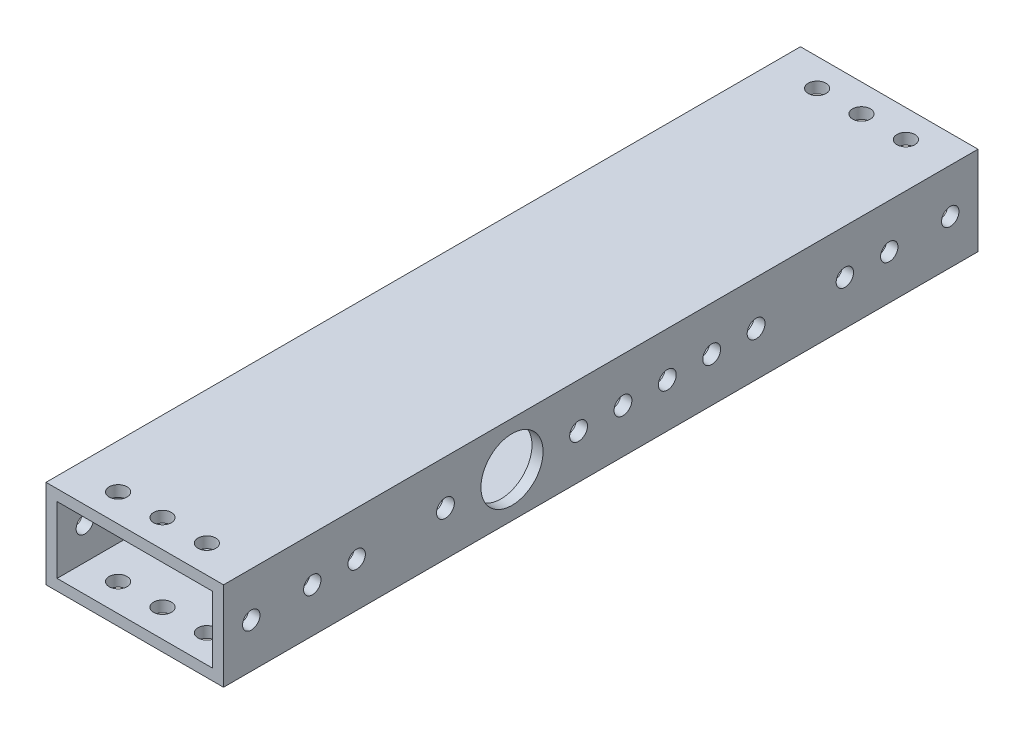
SolidWorks part; units mm, degrees
material "6061-T6 (SS)"
ref_plane "Front Plane" through (0, 0, 0) normal (0, 0, 1) x (1, 0, 0)
ref_plane "Top Plane" through (0, 0, 0) normal (0, 1, 0) x (1, 0, 0)
ref_plane "Right Plane" through (0, 0, 0) normal (1, 0, 0) x (0, 0, -1)
sketch "Sketch1" plane through (0, 0, 0) normal (0, 0, 1) x (1, 0, 0)
  line L0 (-22.225, 9.525) -> (22.225, 9.525)
  line L1 (-25.4, -12.7) -> (25.4, -12.7)
  line L2 (-25.4, -12.7) -> (-25.4, 12.7)
  line L3 (-25.4, 12.7) -> (25.4, 12.7)
  line L4 (25.4, -12.7) -> (25.4, 12.7)
  line L5 (-25.4, -12.7) -> (25.4, 12.7) construction
  line L6 (-25.4, 12.7) -> (25.4, -12.7) construction
  line L7 (22.225, -9.525) -> (22.225, 9.525)
  line L8 (-22.225, -9.525) -> (22.225, -9.525)
  line L9 (-22.225, -9.525) -> (-22.225, 9.525)
  point P0 (0, 0)
  dimension "D1" = 50.8
  dimension "D2" = 25.4
  dimension "D3" = 3.175
extrude "Boss-Extrude1" add sketch "Sketch1" along normal mid plane 215.9
sketch "Sketch3" plane through (0, 12.7, 0) normal (0, 1, 0) x (1, 0, 0)
  line L0 (-25.4, 0) -> (25.4, 0) construction
  line L1 (-25.4, -107.95) -> (-25.4, 107.95) construction
  line L2 (25.4, -107.95) -> (25.4, 107.95) construction
  line L3 (25.4, -107.95) -> (-25.4, -107.95) construction
  circle A0 centre (-12.7, -100.0125) radius 2.5527
  circle A1 centre (0, -100.0125) radius 2.5527
  circle A2 centre (12.7, -100.0125) radius 2.5527
  circle A3 centre (12.7, 100.0125) radius 2.5527
  circle A4 centre (0, 100.0125) radius 2.5527
  circle A5 centre (-12.7, 100.0125) radius 2.5527
  dimension "D1" = 5.1054
  dimension "D2" = 12.7
  dimension "D3" = 12.7
  dimension "D4" = 7.9375
extrude "Cut-Extrude2" cut sketch "Sketch3" against normal through all
sketch "Sketch4" plane through (25.4, 0, 0) normal (1, 0, 0) x (0, 0, -1)
  line L0 (-25.4, 0) -> (-45.1908, 0) construction
  line L1 (-16.51, 0) -> (-34.29, 0) construction
  line L8 (-25.4, 0) -> (31.75, 0) construction
  line L9 (0, 12.7) -> (0, -12.7) construction
  line L10 (-107.95, 12.7) -> (107.95, 12.7) construction
  line L11 (-107.95, -12.7) -> (107.95, -12.7) construction
  circle A0 centre (-25.4, 0) radius 8.89
  circle A9 centre (31.75, 0) radius 2.5527
  circle A10 centre (19.05, 0) radius 2.5527
  dimension "D2" = 17.78
  dimension "D3" = 25.4
  dimension "D1" = 57.15
  dimension "D4" = 5.1054
  dimension "D6" = 44.45
extrude "Cut-Extrude3" cut sketch "Sketch4" against normal through all contours A0 | A9 | A10
sketch "Sketch2" plane through (25.4, 0, 0) normal (1, 0, 0) x (0, 0, -1)
  line L0 (-107.95, -12.7) -> (-107.95, 12.7) construction
  line L1 (0, 12.7) -> (0, -12.7) construction
  line L2 (-107.95, 12.7) -> (107.95, 12.7) construction
  line L3 (-107.95, -12.7) -> (107.95, -12.7) construction
  circle A0 centre (-100.0125, 0) radius 2.4892
  circle A1 centre (100.0125, 0) radius 2.4892
  circle A2 centre (-82.55, 0) radius 2.4892
  circle A3 centre (-69.85, 0) radius 2.4892
  circle A4 centre (69.85, 0) radius 2.4892
  circle A5 centre (82.55, 0) radius 2.4892
  dimension "D2" = 4.9784
  dimension "D5" = 4.9784
  dimension "D4" = 25.4
  dimension "D1" = 7.9375
  dimension "D3" = 12.7
extrude "Cut-Extrude1" cut sketch "Sketch2" against normal through all
sketch "Sketch5" plane through (0, -12.7, 0) normal (0, -1, 0) x (1, 0, 0)
  line L0 (-25.4, 107.95) -> (-25.4, -107.95) construction
  line L1 (-25.4, 107.95) -> (25.4, 107.95) construction
  line L4 (25.4, 25.4) -> (-25.4, 25.4) construction
  line L5 (25.4, 107.95) -> (25.4, -107.95) construction
  circle A0 centre (-3.81, 69.85) radius 2.4892
  circle A1 centre (-16.51, 69.85) radius 2.4892
  circle A2 centre (-16.51, 57.15) radius 2.4892
  circle A3 centre (-3.81, 57.15) radius 2.4892
  circle A8 centre (-3.81, -6.35) radius 2.4892
  circle A9 centre (-16.51, -6.35) radius 2.4892
  circle A10 centre (-16.51, -19.05) radius 2.4892
  circle A11 centre (-3.81, -19.05) radius 2.4892
  dimension "D3" = 4.9784
  dimension "D4" = 8.89
  dimension "D7" = 12.7
  dimension "D12" = 82.55
  dimension "D5" = 31.75
  dimension "D6" = 12.7
  dimension "D1" = 2
  dimension "D2" = 2
extrude "Cut-Extrude4" cut sketch "Sketch5" against normal up to next
sketch "Sketch7" plane through (25.4, 0, 0) normal (1, 0, 0) x (0, 0, -1)
  circle A0 centre (44.45, 0) radius 2.5527
  circle A1 centre (31.75, 0) radius 2.5527 construction
  circle A5 centre (6.35, 0) radius 2.5527
  circle A6 centre (-6.35, 0) radius 2.5527
  circle A7 centre (-44.45, 0) radius 2.5527
  circle A8 centre (-25.4, 0) radius 8.89 construction
  dimension "D1" = 12.7
  dimension "D2" = 19.05
  dimension "D3" = 19.05
  dimension "D4" = 12.7
extrude "Cut-Extrude5" cut sketch "Sketch7" against normal up to next contours A0 | A7 | A6 | A5
